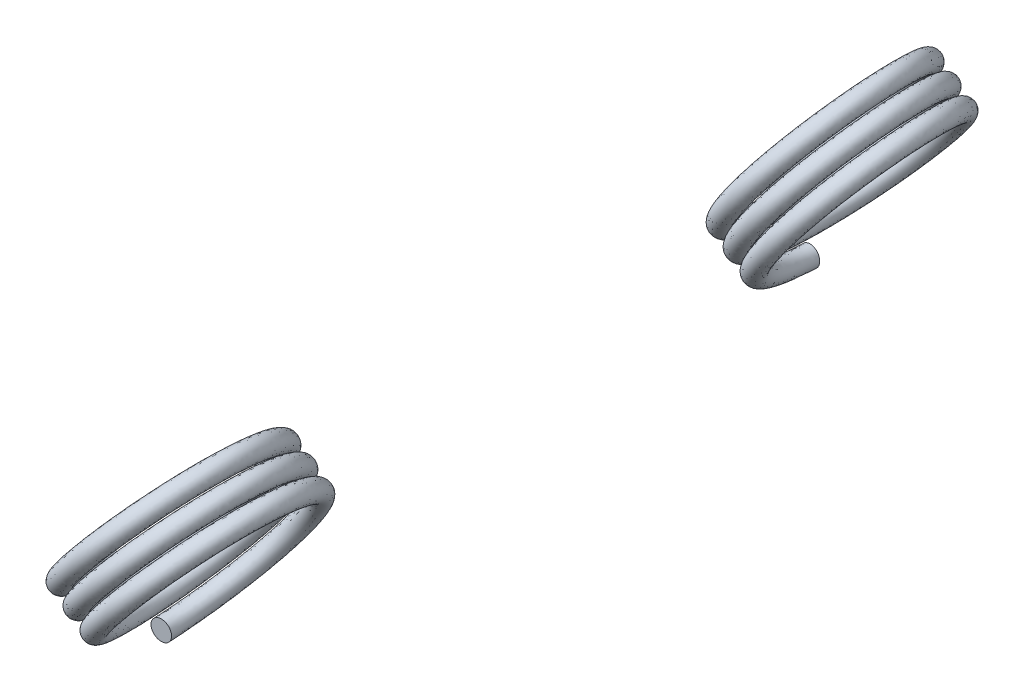
SolidWorks part; units mm, degrees
ref_plane "Alzado" through (0, 0, 0) normal (0, 0, 1) x (1, 0, 0)
ref_plane "Planta" through (0, 0, 0) normal (0, 1, 0) x (1, 0, 0)
ref_plane "Vista lateral" through (0, 0, 0) normal (1, 0, 0) x (0, 0, -1)
sketch3d "Sk_Plano_muelle_izq"
  point P0 (-234.166, 351.0365, 0)
  point P1 (-234.166, 351.0365, 10)
  point P2 (-228.1748, 359.0431, 0)
ref_plane "Plano_muelle_izq" through (-318.5014, 238.3334, 0) normal (-0.8007, 0.5991, 0) x (0, 0, 1)
sketch "Sk_muelle_izq" plane through (-318.5014, 238.3334, 0) normal (-0.8007, 0.5991, 0) x (0, 0, 1)
  circle A0 centre (-26, 140.7638) radius 7.5
  dimension "DIAM1" = 15
curve "Helice_izq" pitch 1.7 height 5.1 turns 3
sweep "Muelle_izq" add path "Helice_izq" circular profile diameter 1.6 parameters "D3"=1.6
sketch3d "Sk_Plano_muelle_dcho"
  point P0 (-234.166, 351.0365, 0)
  point P1 (-234.166, 351.0365, 10)
  point P2 (-228.1748, 359.0431, 0)
ref_plane "Plano_muelle_dcho" through (-318.5014, 238.3334, 0) normal (-0.8007, 0.5991, 0) x (0, 0, 1)
sketch "Sk_muelle_dcho" plane through (-318.5014, 238.3334, 0) normal (-0.8007, 0.5991, 0) x (0, 0, 1)
  circle A0 centre (26, 140.7638) radius 7.5
  dimension "DIAM2" = 15
curve "Helice_dcho" pitch 1.7 height 5.1 turns 3
sweep "Muelle_dcho" add path "Helice_dcho" circular profile diameter 1.6 parameters "D3"=1.6
